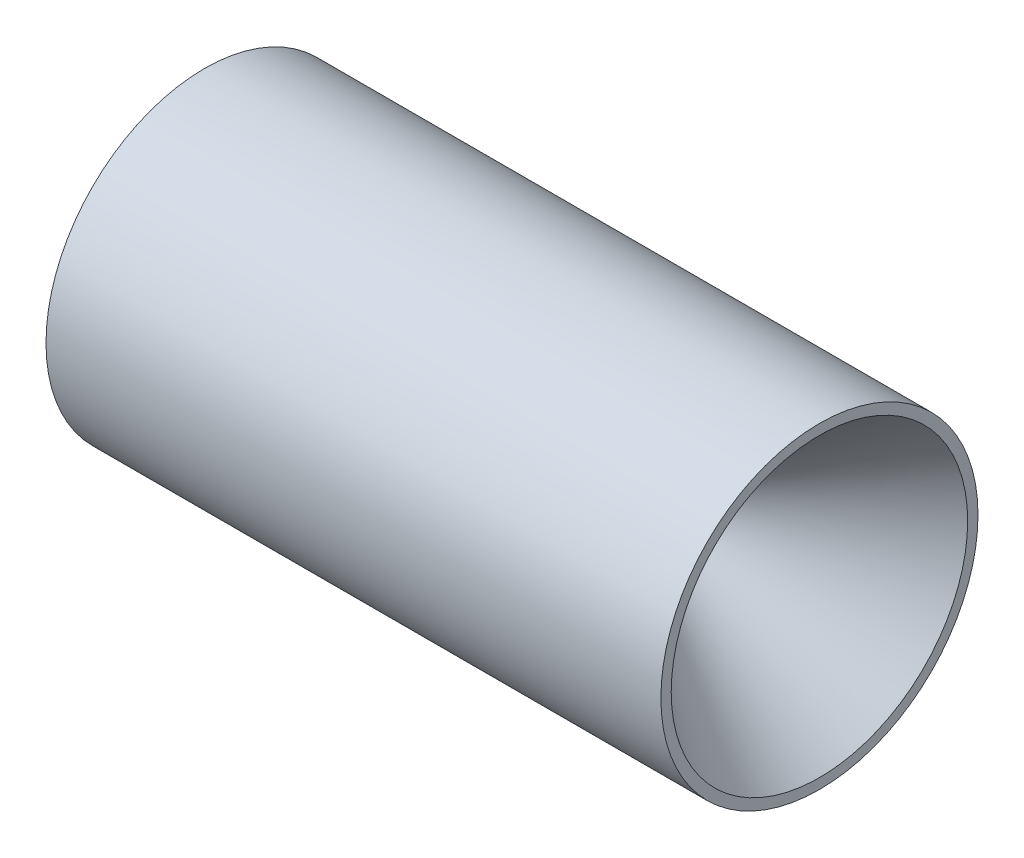
SolidWorks part; units mm, degrees
material "C (Graphite)"
ref_plane "Front Plane" through (0, 0, 0) normal (0, 0, 1) x (1, 0, 0)
ref_plane "Top Plane" through (0, 0, 0) normal (0, 1, 0) x (1, 0, 0)
ref_plane "Right Plane" through (0, 0, 0) normal (1, 0, 0) x (0, 0, -1)
sketch "Sketch1" plane through (0, 0, 0) normal (1, 0, 0) x (0, 0, -1)
  circle A0 centre (0, 0) radius 45.847
  dimension "D1" = 91.694
extrude "Boss-Extrude1" add sketch "Sketch1" along normal blind 177.8
sketch "Sketch3" plane through (0, 0, 0) normal (0, 0, 1) x (1, 0, 0)
  line L0 (0, 0) -> (197.8728, 0) construction
  line L1 (0, 0) -> (0, 42.8625)
  line L2 (0, 45.847) -> (0, -45.847) construction
  line L3 (0, 42.8625) -> (127, 9.525)
  line L4 (127, 9.525) -> (133.35, 9.525)
  line L5 (133.35, 9.525) -> (177.8, 42.8625)
  line L6 (177.8, -45.847) -> (177.8, 45.847) construction
  line L7 (177.8, 42.8625) -> (177.8, 0)
  line L8 (177.8, 0) -> (0, 0)
  line L9 (177.8, 45.847) -> (0, 45.847) construction
  dimension "D1" = 2.9845
  dimension "D2" = 2.9845
  dimension "D3" = 9.525
  dimension "D4" = 44.45
  dimension "D5" = 6.35
revolve "Cut-Revolve1" cut sketch "Sketch3" angle 360 about L0
